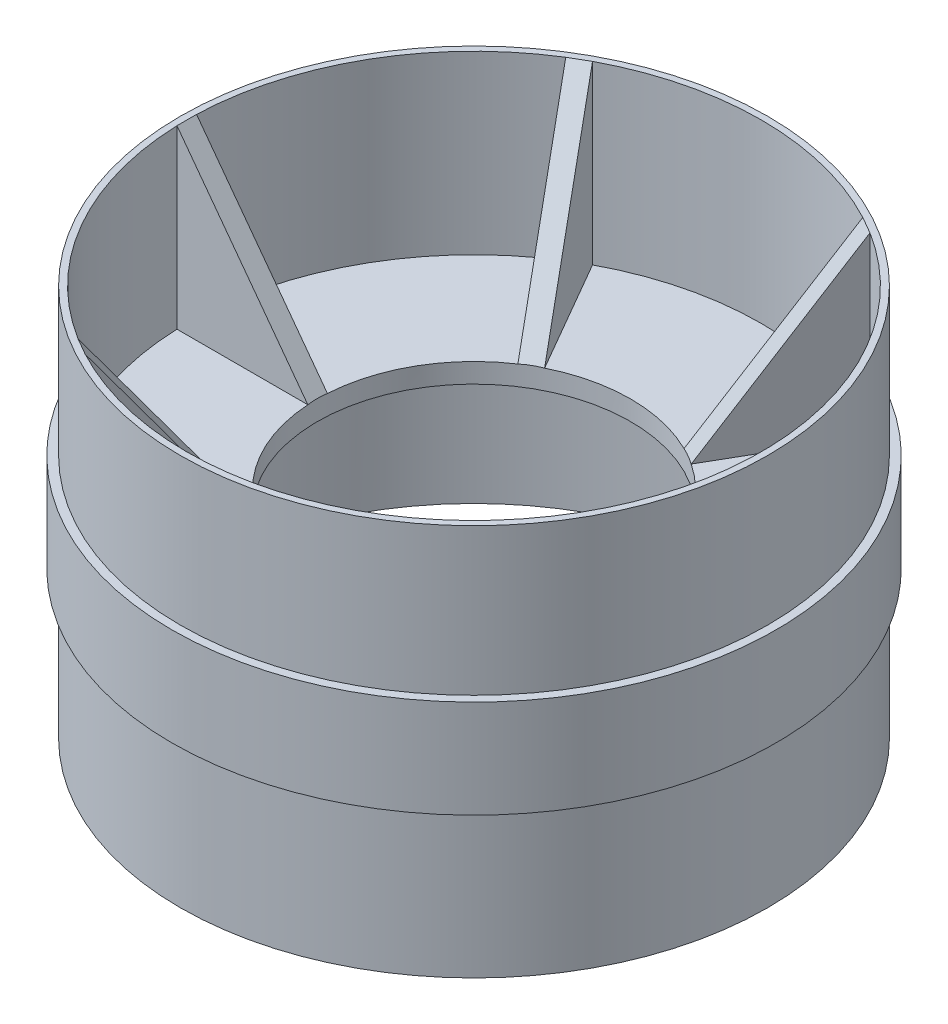
SolidWorks part; units mm, degrees
ref_plane "Front Plane" through (0, 0, 0) normal (0, 0, 1) x (1, 0, 0)
ref_plane "Top Plane" through (0, 0, 0) normal (0, 1, 0) x (1, 0, 0)
ref_plane "Right Plane" through (0, 0, 0) normal (1, 0, 0) x (0, 0, -1)
sketch "Sketch1" plane through (0, 0, 0) normal (0, 1, 0) x (1, 0, 0)
  circle A0 centre (0, 0) radius 74.549
  circle A1 centre (0, 0) radius 78.359
  dimension "D1" = 149.098
  dimension "D2" = 156.718
extrude "Boss-Extrude1" add sketch "Sketch1" along normal blind 25.4
sketch "Sketch2" plane through (0, 25.4, 0) normal (0, 1, 0) x (1, 0, 0)
  circle A0 centre (0, 0) radius 76.2
  circle A1 centre (0, 0) radius 74.549
extrude "Boss-Extrude2" add sketch "Sketch2" along normal blind 38.1
sketch "Sketch3" plane through (0, 0, 0) normal (0, -1, 0) x (1, 0, 0)
  circle A0 centre (0, 0) radius 76.2
  circle A1 centre (0, 0) radius 74.549
  dimension "D1" = 152.4
extrude "Boss-Extrude3" add sketch "Sketch3" along normal blind 38.1
ref_plane "Plane1" through (0, 12.7, 0) normal (0, 1, 0) x (1, 0, 0)
sketch "Sketch4" plane through (0, 12.7, 0) normal (0, 1, 0) x (1, 0, 0)
  circle A0 centre (0, 0) radius 74.549
  circle A1 centre (0, 0) radius 40.64
  dimension "D1" = 81.28
extrude "Boss-Extrude4" add sketch "Sketch4" along normal blind 5.08
sketch "Sketch5" plane through (0, 17.78, 0) normal (0, 1, 0) x (1, 0, 0)
  line L0 (40.5605, 2.54) -> (74.5057, 2.54)
  line L2 (74.5057, -2.54) -> (40.5605, -2.54)
  line L3 (34.8136, 0) -> (44.1618, 0) construction
  line L19 (22.48, -33.8565) -> (39.4526, -63.2538)
  line L20 (35.0532, -65.7938) -> (18.0806, -36.3965)
  line L21 (-18.0806, -36.3965) -> (-35.0532, -65.7938)
  line L22 (-39.4526, -63.2538) -> (-22.48, -33.8565)
  line L29 (-40.5605, -2.54) -> (-74.5057, -2.54)
  line L30 (-74.5057, 2.54) -> (-40.5605, 2.54)
  line L31 (-22.48, 33.8565) -> (-39.4526, 63.2538)
  line L32 (-35.0532, 65.7938) -> (-18.0806, 36.3965)
  line L33 (18.0806, 36.3965) -> (35.0532, 65.7938)
  line L34 (39.4526, 63.2538) -> (22.48, 33.8565)
  circle A0 centre (0, 0) radius 40.64 construction
  arc A1 (39.4526, -63.2538) -> (35.0532, -65.7938) centre (0, 0) cw
  arc A2 (74.5057, 2.54) -> (74.5057, -2.54) centre (0, 0) cw
  circle A3 centre (0, 0) radius 74.549 construction
  arc A4 (40.5605, 2.54) -> (40.5605, -2.54) centre (0, 0) cw
  arc A19 (22.48, -33.8565) -> (18.0806, -36.3965) centre (0, 0) cw
  arc A20 (-35.0532, -65.7938) -> (-39.4526, -63.2538) centre (0, 0) cw
  arc A21 (-18.0806, -36.3965) -> (-22.48, -33.8565) centre (0, 0) cw
  arc A28 (-74.5057, -2.54) -> (-74.5057, 2.54) centre (0, 0) cw
  arc A29 (-40.5605, -2.54) -> (-40.5605, 2.54) centre (0, 0) cw
  arc A30 (-39.4526, 63.2538) -> (-35.0532, 65.7938) centre (0, 0) cw
  arc A31 (-22.48, 33.8565) -> (-18.0806, 36.3965) centre (0, 0) cw
  arc A32 (35.0532, 65.7938) -> (39.4526, 63.2538) centre (0, 0) cw
  arc A33 (18.0806, 36.3965) -> (22.48, 33.8565) centre (0, 0) cw
  point P34 (0, 0)
  point P40 (0, 0)
  dimension "D4" = 0
  dimension "D1" = 2.54
  dimension "D2" = 2.54
  dimension "D3" = 6
extrude "Boss-Extrude10" add sketch "Sketch5" along normal blind 45.72
sketch "Sketch6" plane through (0, 0, 2.54) normal (0, 0, 1) x (1, 0, 0)
  line L0 (74.5057, 63.5) -> (40.5605, 17.78)
  line L1 (40.5605, 17.78) -> (40.5605, 63.5)
  line L2 (40.5605, 63.5) -> (74.5057, 63.5)
extrude "Cut-Extrude1" cut sketch "Sketch6" against normal blind 5.08
pattern_circular "CirPattern1" count 6 over 360 about axis through (0, 12.7, 0) along (0, 1, 0) of "Cut-Extrude1"
